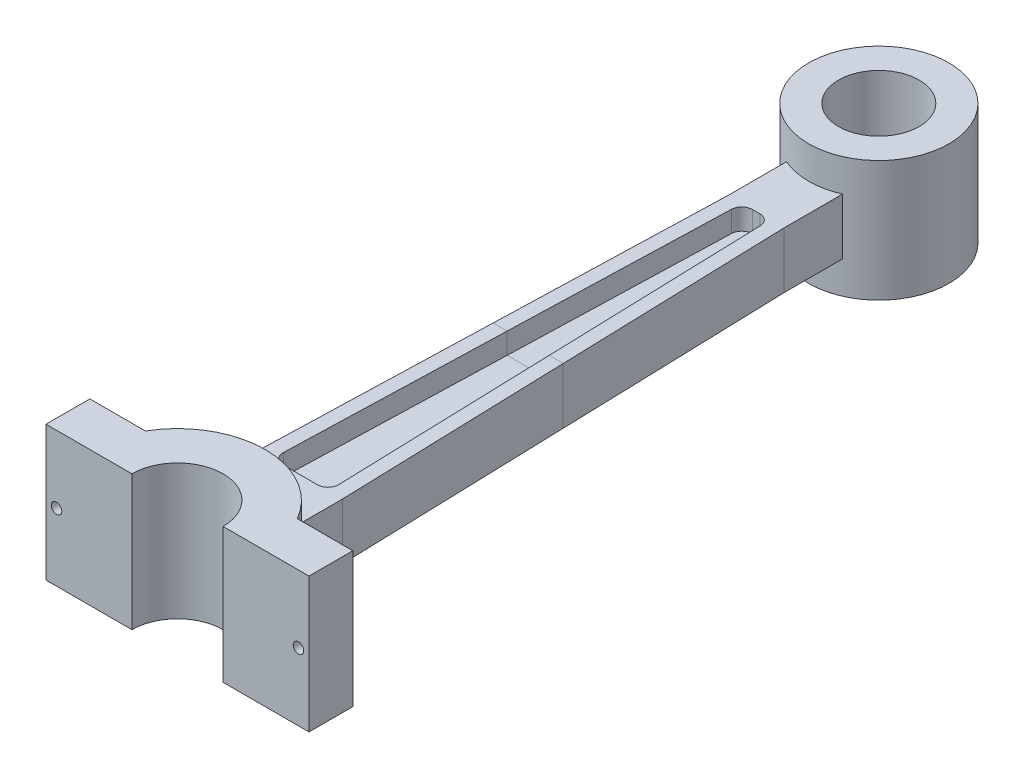
SolidWorks part; units mm, degrees
ref_plane "Front Plane" through (0, 0, 0) normal (0, 0, 1) x (1, 0, 0)
ref_plane "Top Plane" through (0, 0, 0) normal (0, 1, 0) x (1, 0, 0)
ref_plane "Right Plane" through (0, 0, 0) normal (1, 0, 0) x (0, 0, -1)
sketch "Sketch1" plane through (0, 0, 0) normal (0, 1, 0) x (1, 0, 0)
  line L0 (-50, -200) -> (50, -200)
  line L1 (0, -200) -> (0, 0) construction
  line L2 (0, 0) -> (0, 200) construction
  circle A0 centre (0, 200) radius 23
  arc A1 (50, -200) -> (-50, -200) centre (0, -200) ccw
  arc A2 (26, -200) -> (-26, -200) centre (0, -200) ccw
  circle A3 centre (0, 200) radius 40
  dimension "D1" = 50
  dimension "D2" = 46
  dimension "D3" = 26
  dimension "D5" = 80
  dimension "D4" = 400
extrude "Boss-Extrude1" add sketch "Sketch1" along normal blind 34.5 and the other way blind 34.5 contours A3 A0 region at (-38.8686, 0, -200)
extrude "Boss-Extrude2" add sketch "Sketch1<6>" along normal blind 38.5 and the other way blind 38.5 separate body contours A2 L0 A1 region at (0, 0, 151.118)
sketch "Sketch1<6>" plane through (0, 0, 0) normal (0, 1, 0) x (1, 0, 0) same geometry as "Sketch1"
ref_plane "Plane1" through (0, 0, 130) normal (0, 0, 1) x (1, 0, 0)
ref_plane "Plane2" through (0, 0, -130) normal (0, 0, 1) x (1, 0, 0)
sketch "Sketch2" plane through (0, 0, -130) normal (0, 0, 1) x (1, 0, 0)
  line L0 (16, 16) -> (8, 16)
  line L1 (8, 16) -> (8, 4)
  line L2 (8, 4) -> (-8, 4)
  line L3 (-8, 4) -> (-8, 16)
  line L4 (-8, 16) -> (-16, 16)
  line L5 (-16, 16) -> (-16, -16)
  line L6 (-16, 0) -> (0, 0) construction
  line L7 (0, 0) -> (16, 0) construction
  line L8 (16, -16) -> (16, 16)
  line L9 (16, -16) -> (8, -16)
  line L10 (8, -16) -> (8, -4)
  line L11 (-8, -4) -> (-8, -16)
  line L12 (8, -4) -> (-8, -4)
  line L13 (-8, -16) -> (-16, -16)
  dimension "D1" = 8
  dimension "D2" = 8
  dimension "D3" = 16
  dimension "D4" = 16
  dimension "D5" = 4
  dimension "D6" = 32
sketch "Sketch3" plane through (0, 0, 130) normal (0, 0, 1) x (1, 0, 0)
  line L0 (-24, -16) -> (-24, 16)
  line L1 (-24, 16) -> (-16, 16)
  line L2 (-16, 16) -> (-16, 4)
  line L3 (-16, 4) -> (16, 4)
  line L4 (16, 4) -> (16, 16)
  line L5 (16, 16) -> (24, 16)
  line L6 (24, 16) -> (24, -16)
  line L7 (40, 0) -> (-40, 0) construction
  line L8 (24, 0) -> (0, 0) construction
  line L9 (0, 0) -> (-24, 0) construction
  line L10 (16, -16) -> (24, -16)
  line L11 (16, -4) -> (16, -16)
  line L12 (-16, -4) -> (16, -4)
  line L13 (-16, -16) -> (-16, -4)
  line L14 (-24, -16) -> (-16, -16)
  dimension "D1" = 8
  dimension "D2" = 8
  dimension "D3" = 16
  dimension "D4" = 4
  dimension "D5" = 48
sketch "Sketch4" plane through (0, 0, 0) normal (0, 0, 1) x (1, 0, 0)
  line L0 (-20, 16) -> (-12, 16)
  line L1 (-12, 16) -> (-12, 4)
  line L2 (-12, 4) -> (12, 4)
  line L3 (12, 4) -> (12, 16)
  line L4 (12, 16) -> (20, 16)
  line L5 (20, 16) -> (20, -16)
  line L6 (20, 0) -> (0, 0) construction
  line L7 (0, 0) -> (-20, 0) construction
  line L8 (-20, -16) -> (-20, 16)
  line L9 (12, -16) -> (20, -16)
  line L10 (12, -4) -> (12, -16)
  line L11 (-12, -4) -> (12, -4)
  line L12 (-12, -16) -> (-12, -4)
  line L13 (-20, -16) -> (-12, -16)
  dimension "D1" = 8
  dimension "D2" = 8
  dimension "D3" = 4
  dimension "D4" = 40
  dimension "D5" = 16
loft "Loft1" add profiles "Sketch3", "Sketch4"
loft "Loft3" add profiles "Sketch4<3>", "Sketch2"
sketch "Sketch4<3>" plane through (0, 0, 0) normal (0, 0, 1) x (1, 0, 0) same geometry as "Sketch4"
extrude "Boss-Extrude4" add sketch "Sketch2<8>" against normal up to surface (48.4361 mm away) up to face at (0, -34.5, -177)
sketch "Sketch2<8>" plane through (0, 0, -130) normal (0, 0, 1) x (1, 0, 0) same geometry as "Sketch2"
extrude "Boss-Extrude5" add sketch "Sketch3<3>" along normal up to surface (60 mm away) up to face at (0, 0, 187)
sketch "Sketch3<3>" plane through (0, 0, 130) normal (0, 0, 1) x (1, 0, 0) same geometry as "Sketch3"
sketch "Sketch5" plane through (0, 0, 200) normal (0, 0, 1) x (1, 0, 0)
  line L0 (50, 38.5) -> (75, 38.5)
  line L1 (75, 38.5) -> (75, -38.5)
  line L2 (75, -38.5) -> (50, -38.5)
  line L3 (0, 0) -> (0, 38.5) construction
  line L4 (0, 38.5) -> (50, 38.5) construction
  line L6 (-75, -38.5) -> (-50, -38.5)
  line L7 (-75, 38.5) -> (-75, -38.5)
  line L8 (-50, 38.5) -> (-75, 38.5)
  line L9 (-50, 38.5) -> (-50, -38.5)
  line L10 (50, -38.5) -> (50, 38.5)
  line L11 (-50, 38.5) -> (-38, 38.5)
  line L12 (-50, 38.5) -> (-26, 38.5) construction
  line L13 (-38, 38.5) -> (-38, -38.5)
  line L14 (-50, -38.5) -> (-26, -38.5) construction
  line L15 (-38, -38.5) -> (-50, -38.5)
  line L16 (50, -38.5) -> (38, -38.5)
  line L17 (26, -38.5) -> (50, -38.5) construction
  line L18 (38, -38.5) -> (38, 38.5)
  line L19 (38, 38.5) -> (50, 38.5)
  circle A0 centre (69, 0) radius 3 construction
  circle A1 centre (69, 0) radius 3
  circle A2 centre (-69, 0) radius 3
  line M6 (50, -38.5) -> (50, 38.5)
  line M7 (50, 38.5) -> (26, 38.5)
  line M9 (26, -38.5) -> (50, -38.5)
extrude "Boss-Extrude6" add sketch "Sketch5" against normal blind 25 contours L2 L1 L0 A1 M6 | L18 M9 M6 M7 | L15 L13 L11 L9 | L9 L8 L7 L6 A2 region at (62.4031, 0, 200) region at (44, 0, 200) region at (-62.4031, 0, 200) region at (-44, 0, 200)
sketch "Sketch7" plane through (24, 0, 0) normal (1, 0, 0) x (0, 0, -1)
  line L4 (-156.1366, 16) -> (-156.1366, -16)
  line L5 (-156.1366, -16) -> (-130, -16)
  line L6 (-130, -16) -> (-130, 16)
  line L7 (-130, 16) -> (-156.1366, 16)
  line L8 (-156.1366, 16) -> (-156.1366, -16)
  line L9 (-156.1366, -16) -> (-130, -16)
  line L10 (-130, -16) -> (-130, 16)
  line L11 (-130, 16) -> (-156.1366, 16)
  dimension "D1" = 0
extrude "Boss-Extrude7" add sketch "Sketch7" against normal blind 46
fillet "Fillet1" radius 6 4 edges at (16, 10, 130) (-16, 10, 130) (-16, -10, 130) (16, -10, 130)
sketch "Sketch8" plane through (16, 0, 0) normal (1, 0, 0) x (0, 0, -1)
  line L4 (130, -16) -> (163.3394, -16)
  line L5 (163.3394, -16) -> (163.3394, 16)
  line L6 (163.3394, 16) -> (130, 16)
  line L7 (130, 16) -> (130, -16)
  line L8 (130, -16) -> (163.3394, -16)
  line L9 (163.3394, -16) -> (163.3394, 16)
  line L10 (163.3394, 16) -> (130, 16)
  line L11 (130, 16) -> (130, -16)
  dimension "D1" = 0
extrude "Boss-Extrude8" add sketch "Sketch8" against normal blind 30
fillet "Fillet2" radius 6 4 edges at (-8, -10, -130) (8, -10, -130) (-8, 10, -130) (8, 10, -130)
